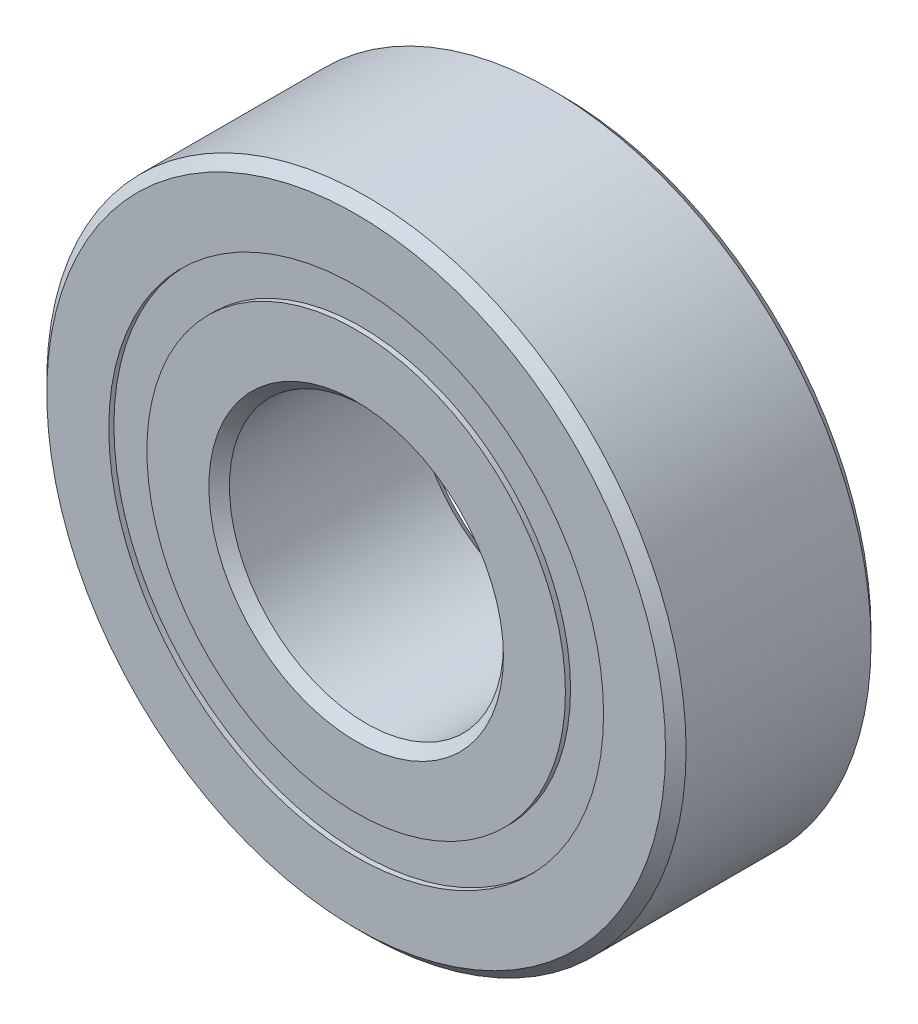
SolidWorks part; units mm, degrees
ref_plane "Front Plane" through (0, 0, 0) normal (0, 0, 1) x (1, 0, 0)
ref_plane "Top Plane" through (0, 0, 0) normal (0, 1, 0) x (1, 0, 0)
ref_plane "Right Plane" through (0, 0, 0) normal (1, 0, 0) x (0, 0, -1)
sketch "Sketch1" plane through (0, 0, 0) normal (1, 0, 0) x (0, 0, -1)
  line L0 (-3.5719, 0) -> (3.5719, 0) construction
  line L1 (0, 11.1125) -> (0, -11.1125) construction
  line L2 (3.2147, 11.1125) -> (-3.2147, 11.1125)
  line L3 (-3.2147, 11.1125) -> (-3.5719, 10.7553)
  line L4 (-3.5719, 10.7553) -> (-3.5719, 8.6004)
  line L5 (-3.5719, 8.6004) -> (-1.5875, 8.6004)
  line L6 (3.5719, 8.6004) -> (1.5875, 8.6004)
  line L7 (3.5719, 10.7553) -> (3.5719, 8.6004)
  line L8 (3.2147, 11.1125) -> (3.5719, 10.7553)
  line L9 (0, 11.1125) -> (0, 7.9375) construction
  line L10 (0, 7.9375) -> (0, 4.7625) construction
  arc A0 (-1.5875, 8.6004) -> (1.5875, 8.6004) centre (0, 7.9375) cw
  point P14 (0, 4.7625)
  dimension "Width" = 7.1437
  dimension "OD" = 22.225
  dimension "D1" = 45
  dimension "D2" = 0.3572
  dimension "Shaft Dia" = 9.525
  dimension "D3" = 3.175
  dimension "D4" = 0.6629
revolve "Revolve1" add sketch "Sketch1" angle 360 about L0
sketch "Sketch3" plane through (0, 0, 0) normal (1, 0, 0) x (0, 0, -1)
  line L0 (-3.5719, 7.2746) -> (-1.5875, 7.2746)
  line L1 (0, 11.1125) -> (0, -11.1125) construction
  line L2 (-3.5719, 10.7553) -> (-3.5719, 8.6004) construction
  line L3 (-3.5719, 7.2746) -> (-3.5719, 5.1197)
  line L4 (-3.2147, 11.1125) -> (-3.5719, 10.7553) construction
  line L5 (-3.5719, 5.1197) -> (-3.2147, 4.7625)
  line L6 (-3.2147, 4.7625) -> (3.2147, 4.7625)
  line L7 (3.2147, 11.1125) -> (3.2147, -11.1125) construction
  line L8 (3.2147, 4.7625) -> (3.5719, 5.1197)
  line L9 (3.5719, -10.7553) -> (3.5719, 10.7553) construction
  line L10 (3.5719, 5.1197) -> (3.5719, 7.2746)
  line L11 (3.5719, 7.2746) -> (1.5875, 7.2746)
  line L13 (3.2147, 11.1125) -> (3.5719, 10.7553) construction
  arc A0 (1.5875, 8.6004) -> (-1.5875, 8.6004) centre (0, 7.9375) ccw construction
  arc A1 (1.5875, 7.2746) -> (-1.5875, 7.2746) centre (0, 7.9375) cw
revolve "Revolve3" add sketch "Sketch3" angle 360 about L0
sketch "Sketch4" plane through (0, 0, 0) normal (1, 0, 0) x (0, 0, -1)
  line L0 (-1.7204, 7.9375) -> (1.7204, 7.9375)
  arc A2 (-1.7204, 7.9375) -> (1.7204, 7.9375) centre (0, 7.9375) cw
  arc A3 (1.5875, 8.6004) -> (-1.5875, 8.6004) centre (0, 7.9375) ccw construction
revolve "Revolve4" add sketch "Sketch4" angle 360 about L0
ref_axis "Axis1" through (0, 0, -3.5719) along (0, 0, 1)
pattern_circular "CirPattern1" count 12 every 30 about axis through (0, 0, -3.5719) along (0, 0, 1) of bodies 104
sketch "Sketch5" plane through (0, 0, 0) normal (1, 0, 0) x (0, 0, -1)
  line L0 (-3.5719, 8.6004) -> (-1.5875, 8.6004) construction
  line L1 (-3.3933, 8.6004) -> (-1.7204, 8.6004)
  line L2 (-3.3933, 8.6004) -> (-3.3933, 7.2746)
  line L3 (-3.3933, 7.2746) -> (-1.7204, 7.2746)
  line L4 (-1.7204, 8.6004) -> (-1.7204, 7.2746)
  line L5 (-3.5719, 7.2746) -> (-1.5875, 7.2746) construction
  line L6 (3.5719, 8.6004) -> (1.5875, 8.6004) construction
  line L7 (3.3933, 8.6004) -> (1.7204, 8.6004)
  line L8 (3.3933, 8.6004) -> (3.3933, 7.2746)
  line L9 (3.3933, 7.2746) -> (1.7204, 7.2746)
  line L10 (1.7204, 8.6004) -> (1.7204, 7.2746)
  line L11 (3.5719, 7.2746) -> (1.5875, 7.2746) construction
  line L12 (-3.2147, 11.1125) -> (-3.5719, 10.7553) construction
  point P18 (-3.3933, 10.9339)
revolve "Revolve5" add sketch "Sketch5" angle 360 about L0
equation "\"D2@Sketch1\" = \"Width@Sketch1\"*.05"
equation "\"D3@Sketch1\" = \"Width@Sketch1\"/2.25"
equation "\"D4@Sketch1\" = (((\"OD@Sketch1\"-\"Width@Sketch1\")/2)/3.25)/3.5"
equation "\"D2@CirPattern1\" = 360/\"Balls@CirPattern1\""
